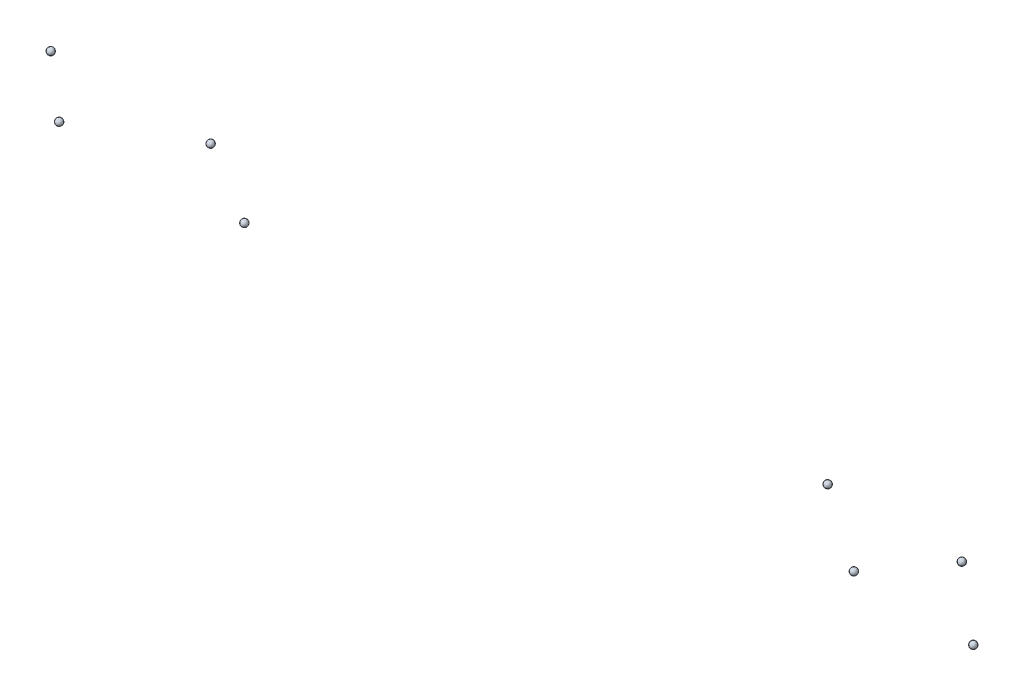
SolidWorks part; units mm, degrees
ref_plane "Front Plane" through (0, 0, 0) normal (0, 0, 1) x (1, 0, 0)
ref_plane "Top Plane" through (0, 0, 0) normal (0, 1, 0) x (1, 0, 0)
ref_plane "Right Plane" through (0, 0, 0) normal (1, 0, 0) x (0, 0, -1)
sketch "Sketch1" plane through (0, 0, 0) normal (0, 1, 0) x (1, 0, 0)
  line L0 (-127, 0) -> (127, 0)
  line L1 (127, 6.35) -> (127, -6.35)
  line L3 (-127, 0) -> (-127, 10.16)
  line L4 (-127, 10.16) -> (-127, 0)
  line L5 (-127, 6.35) -> (-127, -6.35)
  arc A0 (127, -6.35) -> (127, 6.35) centre (127, 0) ccw
  arc A1 (-127, 6.35) -> (-127, -6.35) centre (-127, 0) ccw
  point P2 (0, 0)
  dimension "D2" = 12.7
  dimension "D3" = 10.16
  dimension "D5" = 6.35
  dimension "D1" = 254
  dimension "D4" = 10.16
ref_plane "Plane1" through (127, 0, 0) normal (1, 0, 0) x (0, 0, -1)
sketch "Sketch3" plane through (127, 0, 0) normal (1, 0, 0) x (0, 0, -1)
  line L0 (0, 0) -> (0, -161.925)
  line L1 (0, -161.925) -> (36.322, -161.925)
  dimension "D1" = 161.925
  dimension "D2" = 36.322
ref_plane "Plane2" through (0, 0, -36.322) normal (0, 0, 1) x (1, 0, 0)
sketch "Sketch4" plane through (0, 0, -36.322) normal (0, 0, 1) x (1, 0, 0)
  line L0 (127, -161.925) -> (112.3696, -161.925)
  line L1 (112.3696, -155.575) -> (112.3696, -168.275)
  arc A0 (112.3696, -155.575) -> (112.3696, -168.275) centre (112.3696, -161.925) ccw
  dimension "D2" = 12.7
  dimension "D1" = 14.6304
ref_plane "Plane3" through (-127, 0, 0) normal (1, 0, 0) x (0, 0, -1)
sketch "Sketch5" plane through (-127, 0, 0) normal (1, 0, 0) x (0, 0, -1)
  line L0 (0, 0) -> (0, -152.4)
  line L1 (0, -152.4) -> (34.29, -152.4)
  dimension "D1" = 152.4
  dimension "D2" = 34.29
ref_plane "Plane4" through (0, 0, -34.29) normal (0, 0, 1) x (1, 0, 0)
sketch "Sketch6" plane through (0, 0, -34.29) normal (0, 0, 1) x (1, 0, 0)
  line L0 (-127, -152.4) -> (-111.76, -152.4)
  line L1 (-127, 0) -> (-127, -152.4) construction
  line L2 (-111.76, -158.75) -> (-111.76, -146.05)
  arc A0 (-111.76, -158.75) -> (-111.76, -146.05) centre (-111.76, -152.4) ccw
  dimension "D2" = 12.7
  dimension "D1" = 15.24
revolve "Revolve1" add sketch "Sketch1" angle 360 about L1 region at (129.695, 0, 0)
revolve "Revolve2" add sketch "Sketch1<3>" angle 360 about L5 region at (-129.695, 0, 0)
sketch "Sketch1<3>" plane through (0, 0, 0) normal (0, 1, 0) x (1, 0, 0) same geometry as "Sketch1"
revolve "Revolve3" add sketch "Sketch6" angle 360 about L2 region at (-109.065, -152.4, -34.29)
revolve "Revolve4" add sketch "Sketch4" angle 360 about L1 region at (109.6746, -161.925, -36.322)
sketch "Sketch7" plane through (0, 0, 0) normal (0, 1, 0) x (1, 0, 0)
  line L0 (127, 0) -> (0, -290.9936)
  line L1 (0, -290.9936) -> (-127, 0)
  dimension "D1" = 317.5
  dimension "D2" = 317.5
ref_plane "Plane5" through (0, 0, 290.9936) normal (0, 0, 1) x (1, 0, 0)
sketch "Sketch8" plane through (0, 0, 290.9936) normal (0, 0, 1) x (1, 0, 0)
  line L0 (0, 0) -> (0, -198.12)
  dimension "D1" = 198.12
sketch "Sketch9" plane through (0, 0, 0) normal (0, 1, 0) x (1, 0, 0)
  line L0 (127, 0) -> (-1358.9, 0)
  dimension "D1" = 1485.9
ref_plane "Plane6" through (-1358.9, 0, 0) normal (1, 0, 0) x (0, 0, -1)
sketch "Sketch10" plane through (-1358.9, 0, 0) normal (1, 0, 0) x (0, 0, -1)
  line L0 (0, 0) -> (0, -88.9)
  line L1 (0, -88.9) -> (63.5, -88.9)
  line L2 (63.1553, -82.55) -> (63.1553, -95.25)
  arc A0 (63.1553, -95.25) -> (63.1553, -82.55) centre (63.1553, -88.9) ccw
  dimension "D3" = 12.7
  dimension "D1" = 88.9
  dimension "D2" = 63.5
ref_plane "Plane7" through (0, 0, -63.5) normal (0, 0, 1) x (1, 0, 0)
sketch "Sketch11" plane through (0, 0, -63.5) normal (0, 0, 1) x (1, 0, 0)
  line L0 (-1358.9, -88.9) -> (-1662.1125, -88.9)
  line L1 (-1662.1125, -88.9) -> (-1662.1125, -225.425)
  line L2 (-1358.9, -88.9) -> (-1358.9, -225.425)
  line L3 (-1662.1125, -95.25) -> (-1662.1125, -82.55)
  arc A0 (-1662.1125, -82.55) -> (-1662.1125, -95.25) centre (-1662.1125, -88.9) ccw
  dimension "D4" = 12.7
  dimension "D1" = 303.2125
  dimension "D2" = 136.525
  dimension "D3" = 136.525
ref_plane "Plane8" through (-1662.1125, 0, 0) normal (1, 0, 0) x (0, 0, -1)
sketch "Sketch12" plane through (-1662.1125, 0, 0) normal (1, 0, 0) x (0, 0, -1)
  line L0 (63.5, -225.425) -> (92.075, -225.425)
  dimension "D1" = 28.575
ref_plane "Plane9" through (0, 0, -92.075) normal (0, 0, 1) x (1, 0, 0)
sketch "Sketch13" plane through (0, 0, -92.075) normal (0, 0, 1) x (1, 0, 0)
  line L0 (-1662.1125, -225.425) -> (-1674.8125, -225.425)
  line L1 (-1674.8125, -219.075) -> (-1674.8125, -231.775)
  arc A0 (-1674.8125, -219.075) -> (-1674.8125, -231.775) centre (-1674.8125, -225.425) ccw
  dimension "D2" = 12.7
  dimension "D1" = 12.7
ref_plane "Plane10" through (0, -225.425, 0) normal (0, 1, 0) x (1, 0, 0)
sketch "Sketch14" plane through (0, -225.425, 0) normal (0, 1, 0) x (1, 0, 0)
  line L0 (-1358.9, 63.5) -> (-1358.9, 101.6)
  line L1 (-1358.9, 101.6) -> (-1333.5, 101.6)
  line L2 (-1333.5, 107.95) -> (-1333.5, 95.25)
  arc A0 (-1333.5, 95.25) -> (-1333.5, 107.95) centre (-1333.5, 101.6) ccw
  dimension "D3" = 12.7
  dimension "D1" = 38.1
  dimension "D2" = 25.4
revolve "Revolve5" add sketch "Sketch14" angle 360 about L2 region at (-1330.805, -225.425, -101.6)
revolve "Revolve6" add sketch "Sketch13" angle 360 about L1 region at (-1677.5075, -225.425, -92.075)
revolve "Revolve7" add sketch "Sketch10" angle 360 about L2 region at (-1358.9, -88.9, -65.8504)
revolve "Revolve8" add sketch "Sketch11" angle 360 about L3 region at (-1664.8075, -88.9, -63.5)
